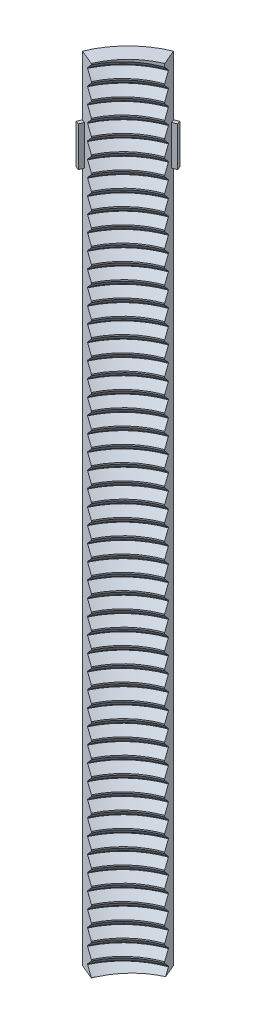
SolidWorks part; units mm, degrees
ref_plane "前视基准面" through (0, 0, 0) normal (0, 0, 1) x (1, 0, 0)
ref_plane "上视基准面" through (0, 0, 0) normal (0, 1, 0) x (1, 0, 0)
ref_plane "右视基准面" through (0, 0, 0) normal (1, 0, 0) x (0, 0, -1)
other "Configuration Table"
sketch "草图1" plane through (0, -839.328, 0) normal (0, 1, 0) x (1, 0, 0)
  line L0 (0, 0) -> (0, 40) construction
  line L1 (-13.0878, 31.5967) -> (-16.264, 39.2649)
  line L2 (-31.5967, 13.0878) -> (-39.2649, 16.264)
  arc A2 (-13.0878, 31.5967) -> (-31.5967, 13.0878) centre (0, 0) ccw
  arc A3 (-16.264, 39.2649) -> (-39.2649, 16.264) centre (0, 0) ccw
  dimension "D5" = 34.2
  dimension "D6" = 42.5
  dimension "D1" = 22.5
  dimension "D2" = 45
extrude "凸台-拉伸1" add sketch "草图1" against normal blind 400
sketch "草图3" plane through (0, -869.328, 0) normal (0, 1, 0) x (1, 0, 0)
  line L0 (-38.4361, 13.3849) -> (-40.136, 13.9768)
  line L1 (-13.3849, 38.4361) -> (-13.9768, 40.136)
  line L4 (-42.5, 0) -> (42.5, 0) construction
  line L5 (0, 0) -> (0, 42.5) construction
  line L9 (-13.0878, 31.5967) -> (-16.264, 39.2649) construction
  line L10 (-39.2649, 16.264) -> (-31.5967, 13.0878) construction
  line L13 (-15.5752, 37.6019) -> (-16.264, 39.2649)
  line L14 (-39.2649, 16.264) -> (-37.6019, 15.5752)
  arc A1 (-37.6019, 15.5752) -> (-38.4361, 13.3849) centre (0, 0) ccw
  arc A2 (-39.2649, 16.264) -> (-40.136, 13.9768) centre (0, 0) ccw
  arc A3 (-13.3849, 38.4361) -> (-15.5752, 37.6019) centre (0, 0) ccw
  arc A4 (-13.9768, 40.136) -> (-16.264, 39.2649) centre (0, 0) ccw
  arc A5 (42.5, 0) -> (-42.5, 0) centre (0, 0) ccw construction
  dimension "D5" = 40.7
  dimension "D1" = 19.2
  dimension "D2" = 19.2
extrude "凸台-拉伸2" add sketch "草图3" against normal blind 20
ref_plane "基准面1" through (0, -843.078, 0) normal (0, 1, 0) x (1, 0, 0)
sketch "草图5" plane through (0, -843.078, 0) normal (0, 1, 0) x (1, 0, 0)
  circle A0 centre (0, 0) radius 34.1
  dimension "D1" = 68.2
curve "螺旋线/涡状线1" pitch 8 height 396.25 turns 49.5312
sketch "草图6" plane through (0, -1839.328, 0) normal (0, 0, 1) x (1, 0, 0)
  line L0 (-34.1, 1000) -> (-34.1, 992.5)
  line L1 (-34.1, 992.5) -> (-37.7, 996.1)
  line L2 (-37.7, 996.1) -> (-37.7, 996.4)
  line L3 (-37.7, 996.4) -> (-34.1, 1000)
  point P2 (-34.1, 996.25)
  dimension "D1" = 7.5
  dimension "D2" = 3.6
  dimension "D3" = 45
  dimension "D4" = 45
sweep "切除-扫描1" cut profiles "草图6" path "螺旋线/涡状线1" align with end faces yes
sketch "草图8" plane through (0, -839.328, 0) normal (0, 1, 0) x (1, 0, 0)
  line L2 (-24.0461, 31.3375) -> (-25.8724, 33.7175) construction
  line L3 (-33.7175, 25.8724) -> (-31.3375, 24.0461) construction
  line L6 (-24.0461, 31.3375) -> (-25.8724, 33.7175) construction
  line L7 (-33.7175, 25.8724) -> (-31.3375, 24.0461) construction
  line L8 (-33.9276, 25.8445) -> (-31.3095, 23.8356)
  line L9 (-23.8356, 31.3095) -> (-25.8445, 33.9276)
  arc A2 (-24.0461, 31.3375) -> (-31.3375, 24.0461) centre (0, 0) ccw construction
  arc A5 (-24.0461, 31.3375) -> (-31.3375, 24.0461) centre (0, 0) ccw construction
  arc A6 (-25.8724, 33.7175) -> (-33.7175, 25.8724) centre (0, 0) ccw construction
  arc A7 (-23.8356, 31.3095) -> (-31.3095, 23.8356) centre (0, 0) ccw
  arc A8 (-25.8445, 33.9276) -> (-33.9276, 25.8445) centre (0, 0) ccw
  dimension "D1" = 0.15
extrude "切除-拉伸1" cut sketch "草图8" against normal blind 370 from offset 30 offset against normal yes
ref_plane "基准面2" through (-30.052, 0, -30.052) normal (-0.7071, 0, -0.7071) x (0, 1, 0)
sketch "草图9" plane through (-30.052, 0, -30.052) normal (-0.7071, 0, -0.7071) x (0, 1, 0)
  circle A0 centre (-859.328, 0) radius 1.25 construction
  circle A1 centre (-859.328, 0) radius 1.25
extrude "切除-拉伸2" cut sketch "草图9" against normal blind 3.5
